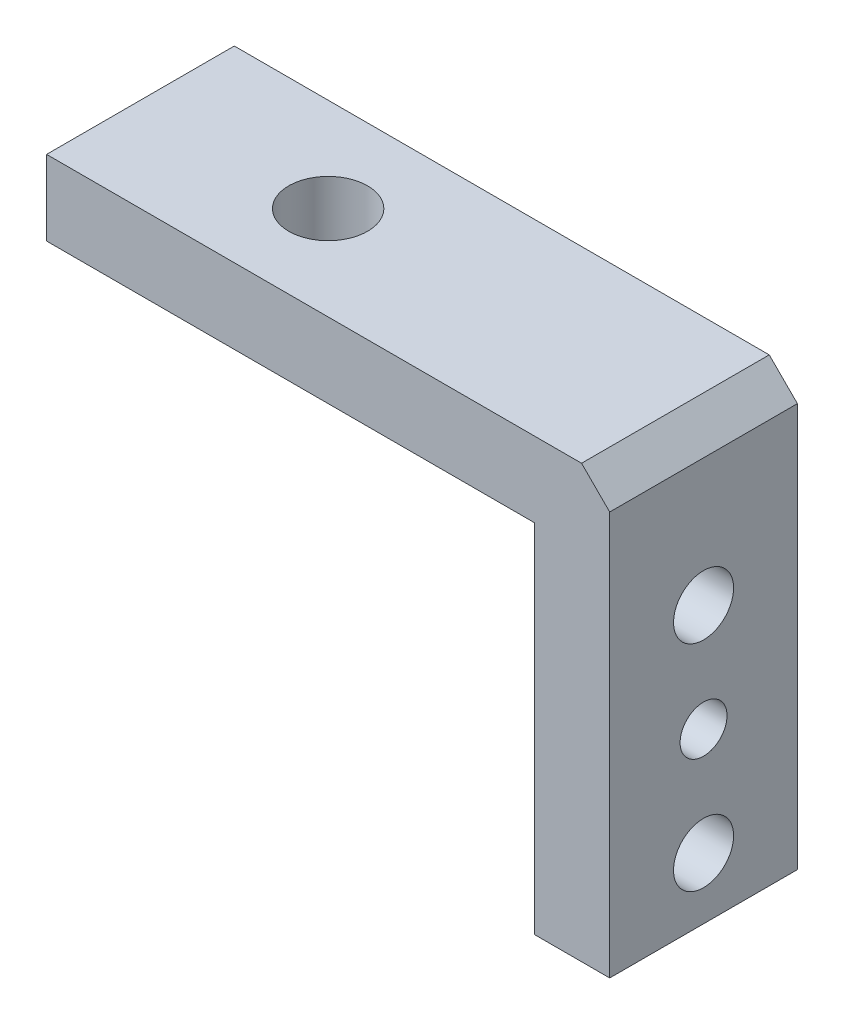
SolidWorks part; units mm, degrees
material "1060 Alloy"
ref_plane "Front Plane" through (0, 0, 0) normal (0, 0, 1) x (1, 0, 0)
ref_plane "Top Plane" through (0, 0, 0) normal (0, 1, 0) x (1, 0, 0)
ref_plane "Right Plane" through (0, 0, 0) normal (1, 0, 0) x (0, 0, -1)
sketch "Sketch1" plane through (0, 0, 0) normal (0, 0, 1) x (1, 0, 0)
  line L1 (15, -11.5) -> (-15, -11.5)
  line L2 (15, -11.5) -> (15, 11.5)
  line L3 (15, 11.5) -> (-15, 11.5)
  line L4 (-15, -11.5) -> (-15, 11.5)
  line L5 (15, -11.5) -> (-15, 11.5) construction
  line L6 (15, 11.5) -> (-15, -11.5) construction
  point P0 (0, 0)
  dimension "D1" = 30
  dimension "D2" = 23
extrude "Boss-Extrude1" add sketch "Sketch1" along normal mid plane 10
sketch "Sketch2" plane through (0, 0, 5) normal (0, 0, 1) x (1, 0, 0)
  line L1 (-15, -11.5) -> (11, -11.5)
  line L2 (-15, -11.5) -> (-15, 7.5)
  line L3 (-15, 7.5) -> (11, 7.5)
  line L4 (11, -11.5) -> (11, 7.5)
  line L5 (-15, -11.5) -> (11, 7.5) construction
  line L6 (-15, 7.5) -> (11, -11.5) construction
  point P4 (-2, -2)
  dimension "D1" = 19
  dimension "D2" = 26
extrude "Cut-Extrude1" cut sketch "Sketch2" against normal through all
chamfer "Chamfer1" distance 1.5 angle 45 1 edges at (15, 11.5, 0)
hole_wizard "Tapped Hole for M4x0.7 Helicoil1" positions "Sketch3" profile "Sketch4" tap size "M4x0.7" standard "Helicoil® Metric" end condition through all
sketch "Sketch3" plane through (0, 11.5, 0) normal (0, 1, 0) x (1, 0, 0)
  line L0 (-15, -5) -> (-15, 5) construction
  point P0 (-5, 0)
  dimension "D1" = 10
sketch "Sketch4" plane through (-5, 11.5, 0) normal (1, 0, 0) x (0, 0, 1)
  line L0 (0, 0) -> (0, 23)
  line L1 (0, 23) -> (2.1, 23)
  line L2 (2.1, 23) -> (2.1, 0)
  line L5 (2.1, 0) -> (0, 0)
  line L11 (0, -6.35) -> (0, 107.95) construction
  dimension "Thru Tap Drill Dia." = 4.2
  dimension "Thru Tap Drill Depth" = 23
cosmetic thread "Hole Thread1" parameters "D1"=4, "D2"=5.007
ref_axis "Axis1" through (-5, 7.5, 0) along (0, 1, 0)
ref_plane "Plane1" through (-5, 0, 0) normal (-1, 0, 0) x (0, 0, 1)
hole_wizard "M3 Clearance Hole1" positions "Sketch5" profile "Sketch6" hole size "M3" standard "ISO" end condition through all
sketch "Sketch5" plane through (15, 0, 0) normal (1, 0, 0) x (0, 0, -1)
  point P0 (0, -8.232)
  point P3 (0, 3.198)
sketch "Sketch6" plane through (15, -8.232, 0) normal (0, 1, 0) x (0, 0, -1)
  line L0 (0, 0) -> (0, 30)
  line L1 (0, 30) -> (1.6, 30)
  line L2 (1.6, 30) -> (1.6, 0)
  line L5 (1.6, 0) -> (0, 0)
  line L11 (0, -6.35) -> (0, 107.95) construction
  dimension "Thru Hole Dia." = 3.2
  dimension "Thru Hole Depth" = 30
hole_wizard "M3 Tapped Hole1" positions "Sketch7" profile "Sketch8" tap size "M3" standard "ISO" end condition through all
sketch "Sketch7" plane through (15, 0, 0) normal (1, 0, 0) x (0, 0, -1)
  line L1 (0, 3.198) -> (0, -8.232) construction
  point P0 (0, -2.517)
sketch "Sketch8" plane through (15, -2.517, 0) normal (0, 1, 0) x (0, 0, -1)
  line L0 (0, 0) -> (0, 30)
  line L1 (0, 30) -> (1.25, 30)
  line L2 (1.25, 30) -> (1.25, 0)
  line L5 (1.25, 0) -> (0, 0)
  line L11 (0, -6.35) -> (0, 107.95) construction
  dimension "Thru Tap Drill Dia." = 2.5
  dimension "Thru Tap Drill Depth" = 30
cosmetic thread "Hole Thread2" parameters "D2"=3
